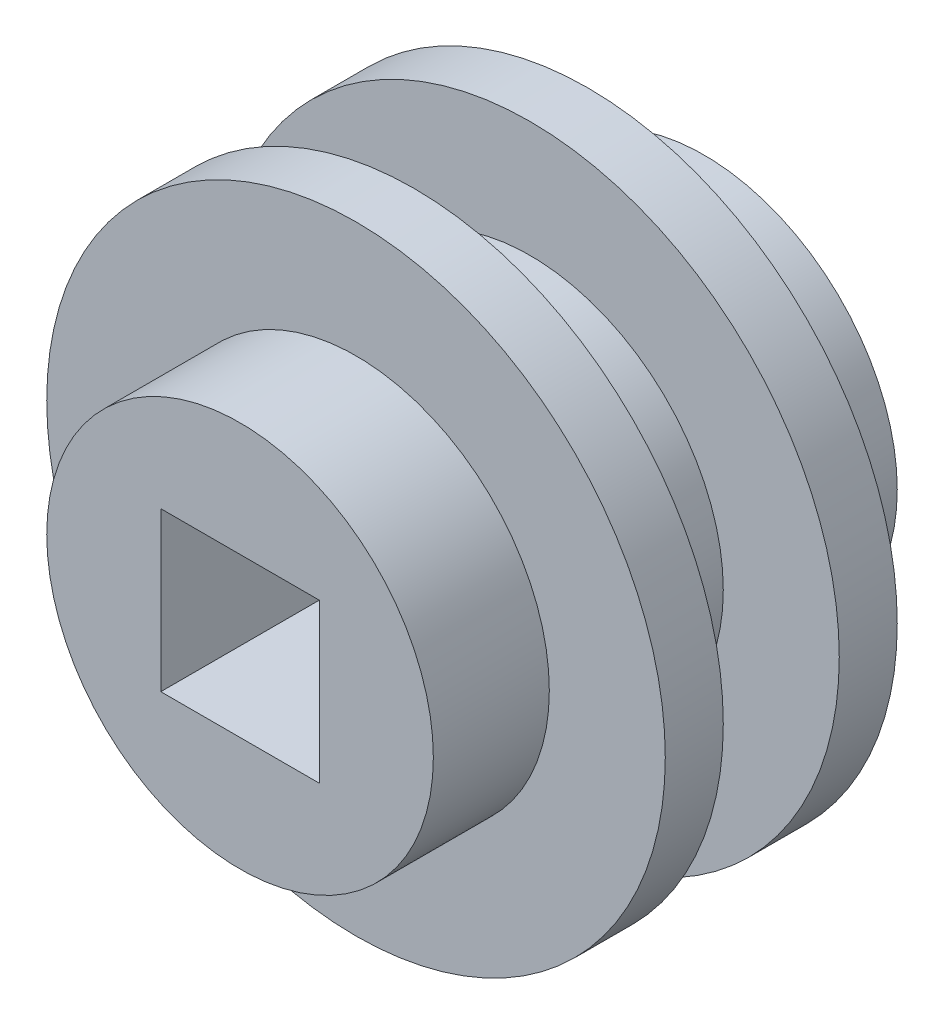
SolidWorks part; units mm, degrees
ref_plane "Front Plane" through (0, 0, 0) normal (0, 0, 1) x (1, 0, 0)
ref_plane "Top Plane" through (0, 0, 0) normal (0, 1, 0) x (1, 0, 0)
ref_plane "Right Plane" through (0, 0, 0) normal (1, 0, 0) x (0, 0, -1)
sketch "Sketch1" plane through (0, 0, 0) normal (0, 0, 1) x (1, 0, 0)
  line L1 (-2.05, -2.05) -> (2.05, -2.05)
  line L2 (-2.05, -2.05) -> (-2.05, 2.05)
  line L3 (-2.05, 2.05) -> (2.05, 2.05)
  line L4 (2.05, -2.05) -> (2.05, 2.05)
  line L5 (-2.05, -2.05) -> (2.05, 2.05) construction
  line L6 (-2.05, 2.05) -> (2.05, -2.05) construction
  circle A0 centre (0, 0) radius 5
  circle A1 centre (0, 0) radius 8
  dimension "D1" = 10
  dimension "D2" = 4.1
  dimension "D3" = 16
extrude "Boss-Extrude1" add sketch "Sketch1" along normal mid plane 12 contours A0 L4 L1 L2 L3 region at (-4.8586, 0, 0)
extrude "Boss-Extrude2" add sketch "Sketch1<3>" along normal mid plane 6 contours A1 A0 | A0 region at (-7.7737, 0, 0)
sketch "Sketch1<3>" plane through (0, 0, 0) normal (0, 0, 1) x (1, 0, 0) same geometry as "Sketch1"
extrude "Cut-Extrude-Thin1" cut sketch "Sketch1<6>" along normal mid plane 3 thin contours A1 thin type one direction reverse wall 3
sketch "Sketch1<6>" plane through (0, 0, 0) normal (0, 0, 1) x (1, 0, 0) same geometry as "Sketch1"
